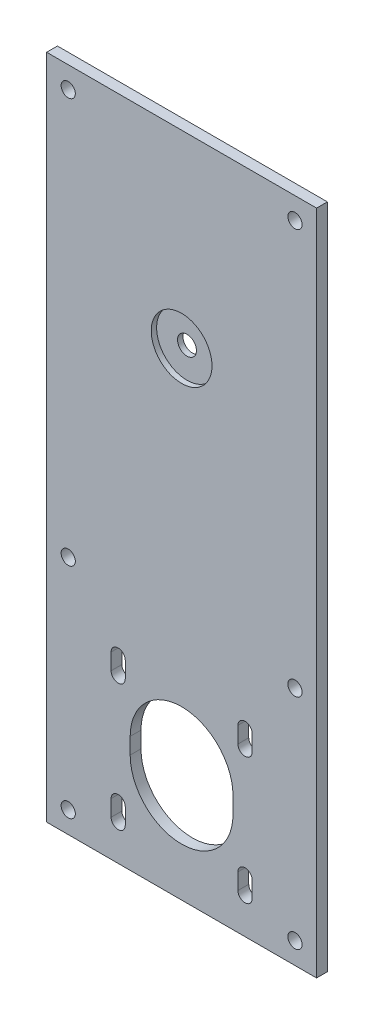
SolidWorks part; units mm, degrees
ref_plane "Front Plane" through (0, 0, 0) normal (0, 0, 1) x (1, 0, 0)
ref_plane "Top Plane" through (0, 0, 0) normal (0, 1, 0) x (1, 0, 0)
ref_plane "Right Plane" through (0, 0, 0) normal (1, 0, 0) x (0, 0, -1)
sketch "Sketch1" plane through (0, 0, 0) normal (0, 0, 1) x (1, 0, 0)
  line L1 (-50, 123.5) -> (50, 123.5)
  line L2 (-50, 123.5) -> (-50, -123.5)
  line L3 (-50, -123.5) -> (50, -123.5)
  line L4 (50, 123.5) -> (50, -123.5)
  line L5 (-50, 123.5) -> (50, -123.5) construction
  line L6 (-50, -123.5) -> (50, 123.5) construction
  line L8 (-19.05, -80.5) -> (-19.05, -86.5)
  line L9 (19.05, -86.5) -> (19.05, -80.5)
  line L10 (-23.5, -57) -> (-23.5, -63) construction
  line L14 (-20.87, -57) -> (-20.87, -63)
  line L15 (-26.13, -57) -> (-26.13, -63)
  line L16 (0, -83.5) -> (41.1398, -83.5) construction
  line L17 (0, -83.5) -> (0, -119.2312) construction
  line L18 (23.5, -57) -> (23.5, -63) construction
  line L19 (20.87, -57) -> (20.87, -63)
  line L20 (26.13, -57) -> (26.13, -63)
  line L21 (23.5, -110) -> (23.5, -104) construction
  line L22 (20.87, -110) -> (20.87, -104)
  line L23 (26.13, -110) -> (26.13, -104)
  line L24 (-23.5, -110) -> (-23.5, -104) construction
  line L25 (-20.87, -110) -> (-20.87, -104)
  line L26 (-26.13, -110) -> (-26.13, -104)
  circle A0 centre (-42, -34.5) radius 2.625
  circle A1 centre (42, -34.5) radius 2.625
  circle A2 centre (-42, -115.5) radius 2.625
  circle A3 centre (42, -115.5) radius 2.625
  arc A6 (19.05, -80.5) -> (-19.05, -80.5) centre (0, -80.5) ccw
  arc A7 (-19.05, -86.5) -> (19.05, -86.5) centre (0, -86.5) ccw
  arc A10 (-20.87, -57) -> (-26.13, -57) centre (-23.5, -57) ccw
  arc A11 (-26.13, -63) -> (-20.87, -63) centre (-23.5, -63) ccw
  arc A12 (20.87, -57) -> (26.13, -57) centre (23.5, -57) cw
  arc A13 (26.13, -63) -> (20.87, -63) centre (23.5, -63) cw
  arc A14 (20.87, -110) -> (26.13, -110) centre (23.5, -110) ccw
  arc A15 (26.13, -104) -> (20.87, -104) centre (23.5, -104) ccw
  arc A16 (-20.87, -110) -> (-26.13, -110) centre (-23.5, -110) cw
  arc A17 (-26.13, -104) -> (-20.87, -104) centre (-23.5, -104) cw
  circle A18 centre (0, 53.5) radius 3.5
  circle A19 centre (42, 115.5) radius 2.625
  circle A20 centre (-42, 115.5) radius 2.625
  circle A21 centre (-14, 67.5) radius 2.625 construction
  circle A22 centre (14, 67.5) radius 2.625 construction
  circle A23 centre (14, 39.5) radius 2.625 construction
  circle A24 centre (-14, 39.5) radius 2.625 construction
  point P0 (0, 0)
  point P14 (-23.5, -60)
  point P17 (0, -83.5)
  point P34 (23.5, -60)
  point P41 (23.5, -107)
  point P48 (-23.5, -107)
  dimension "D3" = 5.25
  dimension "D4" = 81
  dimension "D6" = 5.26
  dimension "D8" = 8
  dimension "D12" = 19.05
  dimension "D14" = 3
  dimension "D15" = 23.5
  dimension "D16" = 7
  dimension "D19" = 5.25
  dimension "D1" = 100
  dimension "D2" = 247
  dimension "D5" = 84
  dimension "D7" = 6
  dimension "D9" = 6
  dimension "D10" = 8
  dimension "D11" = 23.5
  dimension "D13" = 207
  dimension "D17" = 70
  dimension "D18" = 8
  dimension "D20" = 28
  dimension "D21" = 28
  dimension "D22" = 14
  dimension "D23" = 14
extrude "Boss-Extrude1" add sketch "Sketch1" along normal blind 4
sketch "Sketch2" plane through (0, 0, 4) normal (0, 0, 1) x (1, 0, 0)
  circle A0 centre (0, 53.5) radius 11.25
  dimension "D1" = 22.5
extrude "Cut-Extrude1" cut sketch "Sketch2" against normal blind 2
